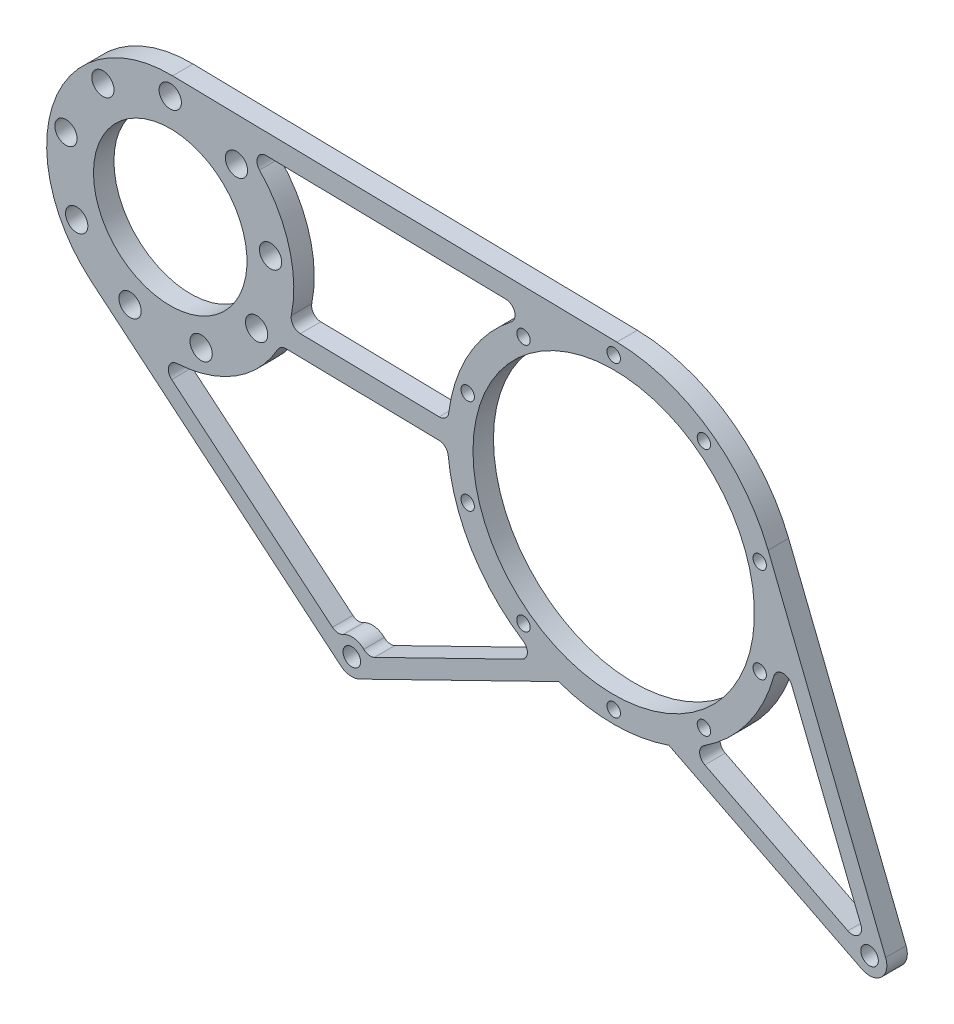
SolidWorks part; units mm, degrees
ref_plane "Front Plane" through (0, 0, 0) normal (0, 0, 1) x (1, 0, 0)
ref_plane "Top Plane" through (0, 0, 0) normal (0, 1, 0) x (1, 0, 0)
ref_plane "Right Plane" through (0, 0, 0) normal (1, 0, 0) x (0, 0, -1)
sketch "Sketch2" plane through (0, 0, 0) normal (0, 0, 1) x (1, 0, 0)
  line L0 (-114.3, 107.95) -> (-114.3, 95.25) construction
  line L1 (-308.8752, 91.6841) -> (-215.9253, 14.1066)
  line L2 (-278.5268, 172.9917) -> (-113.1247, 169.8513)
  line L3 (-13.0706, 21.4387) -> (-56.8054, 130.918)
  line L4 (-208.9705, 13.2659) -> (-134.815, 49.5352)
  line L5 (-21.9498, 13.301) -> (-93.785, 49.5352)
  circle A0 centre (-279.4, 127) radius 28.575
  circle A1 centre (-114.3, 95.25) radius 36 construction
  circle A2 centre (0, 0) radius 12.7 construction
  circle A3 centre (-228.6, 0) radius 12.7 construction
  arc A4 (-278.5268, 172.9917) -> (-308.8752, 91.6841) centre (-279.4, 127) ccw
  arc A5 (-134.815, 49.5352) -> (-93.785, 49.5352) centre (-114.3, 107.95) ccw
  circle A6 centre (-19.05, 19.05) radius 3.2639
  circle A7 centre (-211.7995, 19.05) radius 3.2639
  arc A8 (-215.9253, 14.1066) -> (-208.9705, 13.2659) centre (-211.7995, 19.05) ccw
  arc A9 (-21.9498, 13.301) -> (-13.0706, 21.4387) centre (-19.05, 19.05) ccw
  circle A10 centre (-114.3, 107.95) radius 52.3875
  arc A11 (-56.8054, 130.918) -> (-113.1247, 169.8513) centre (-114.3, 107.95) ccw
  dimension "D1" = 25.4
  dimension "D2" = 25.4
  dimension "D8" = 57.15
  dimension "D9" = 72
  dimension "D10" = 92
  dimension "D12" = 123.825
  dimension "D13" = 6.5278
  dimension "D16" = 6.5278
  dimension "D18" = 3.175
  dimension "D20" = 104.775
  dimension "D3" = 228.6
  dimension "D4" = 114.3
  dimension "D5" = 95.25
  dimension "D6" = 279.4
  dimension "D7" = 127
  dimension "D11" = 12.7
  dimension "D14" = 19.05
  dimension "D15" = 19.05
  dimension "D17" = 25.4
  dimension "D19" = 82.55
extrude "Boss-Extrude1" add sketch "Sketch2" along normal blind 7.62
sketch "Sketch3" plane through (0, 0, 7.62) normal (0, 0, 1) x (1, 0, 0)
  line L0 (-279.4, 127) -> (-279.4, 166.0004) construction
  line L1 (-114.3, 107.95) -> (-114.3, 165.1) construction
  circle A0 centre (-279.4, 127) radius 39.0004 construction
  circle A1 centre (-279.4, 166.0004) radius 4.15
  circle A2 centre (-254.7465, 156.3809) radius 4.15
  circle A3 centre (-242.0442, 133.1649) radius 4.15
  circle A4 centre (-247.2366, 107.2156) radius 4.15
  circle A5 centre (-267.8941, 90.6748) radius 4.15
  circle A6 centre (-294.3509, 91.2822) radius 4.15
  circle A7 centre (-314.2275, 108.7537) radius 4.15
  circle A8 centre (-318.2234, 134.914) radius 4.15
  circle A9 centre (-304.469, 157.5225) radius 4.15
  circle A10 centre (-114.3, 107.95) radius 57.15 construction
  circle A11 centre (-114.3, 165.1) radius 2.5
  circle A12 centre (-80.7081, 154.1853) radius 2.5
  circle A13 centre (-59.9471, 125.6103) radius 2.5
  circle A14 centre (-59.9471, 90.2897) radius 2.5
  circle A15 centre (-80.7081, 61.7147) radius 2.5
  circle A16 centre (-114.3, 50.8) radius 2.5
  circle A17 centre (-147.8919, 61.7147) radius 2.5
  circle A18 centre (-168.6529, 90.2897) radius 2.5
  circle A19 centre (-168.6529, 125.6103) radius 2.5
  circle A20 centre (-147.8919, 154.1853) radius 2.5
  point P24 (-280.288, 127.3232)
  point P48 (-114.3, 107.95)
  dimension "D1" = 78.0009
  dimension "D2" = 8.3
  dimension "D4" = 114.3
  dimension "D5" = 5
  dimension "D3" = 9
  dimension "D6" = 10
extrude "Cut-Extrude1" cut sketch "Sketch3" against normal through all both and the other way through all
sketch "Sketch4" plane through (0, 0, 7.62) normal (0, 0, 1) x (1, 0, 0)
  line L0 (-278.8602, 74.9042) -> (-219.0194, 24.9601)
  line L1 (-48.0193, 91.8071) -> (-22.3039, 27.4349)
  line L2 (-308.8752, 91.6841) -> (-215.9253, 14.1066) construction
  line L3 (-148.3931, 49.9629) -> (-203.3792, 23.0694)
  line L4 (-208.9705, 13.2659) -> (-134.815, 49.5352) construction
  line L5 (-243.5726, 164.7067) -> (-154.4587, 163.0147)
  line L6 (-113.1247, 169.8513) -> (-278.5268, 172.9917) construction
  line L7 (-80.3879, 49.8896) -> (-27.12, 23.021)
  line L8 (-93.785, 49.5352) -> (-21.9498, 13.301) construction
  line L9 (-13.0706, 21.4387) -> (-56.8054, 130.918) construction
  line L10 (-230.9639, 113.6581) -> (-179.2529, 112.6763)
  line L11 (-236.2483, 106.1371) -> (-179.3262, 105.0564)
  arc A0 (-234.3202, 117.8451) -> (-239.355, 104.3639) centre (-279.4, 127) ccw construction
  arc A1 (-175.9167, 101.9055) -> (-175.7218, 115.7294) centre (-114.3, 107.95) ccw construction
  circle A2 centre (-19.05, 19.05) radius 6.4389 construction
  circle A3 centre (-211.7995, 19.05) radius 6.4389 construction
  arc A4 (-278.5268, 172.9917) -> (-308.8752, 91.6841) centre (-279.4, 127) ccw construction
  arc A5 (-246.1625, 158.8004) -> (-234.3202, 117.8451) centre (-279.4, 127) cw
  arc A6 (-152.3771, 156.769) -> (-175.7218, 115.7294) centre (-114.3, 107.95) ccw
  arc A7 (-54.6287, 91.4427) -> (-80.7099, 55.9417) centre (-114.3, 107.95) cw
  arc A8 (-154.4587, 163.0147) -> (-152.3771, 156.769) centre (-154.525, 159.5229) cw
  arc A9 (-243.5726, 164.7067) -> (-246.1625, 158.8004) centre (-243.6389, 161.2148) ccw
  arc A10 (-278.8602, 74.9042) -> (-276.8184, 81.0725) centre (-276.6224, 77.5855) cw
  arc A11 (-148.0251, 56.0292) -> (-148.3931, 49.9629) centre (-149.9276, 53.1003) cw
  arc A12 (-80.3879, 49.8896) -> (-80.7099, 55.9417) centre (-78.8151, 53.0079) cw
  arc A13 (-48.0193, 91.8071) -> (-54.6287, 91.4427) centre (-51.2626, 90.5115) ccw
  arc A14 (-27.12, 23.021) -> (-22.3039, 27.4349) centre (-25.5472, 26.1393) ccw
  arc A15 (-215.0295, 24.6201) -> (-207.3352, 23.69) centre (-211.7995, 19.05) cw
  arc A16 (-203.3792, 23.0694) -> (-207.3352, 23.69) centre (-204.9137, 26.2067) cw
  arc A17 (-219.0194, 24.9601) -> (-215.0295, 24.6201) centre (-216.7815, 27.6414) ccw
  arc A18 (-239.355, 104.3639) -> (-276.8184, 81.0725) centre (-279.4, 127) cw
  arc A19 (-175.9167, 101.9055) -> (-148.0251, 56.0292) centre (-114.3, 107.95) ccw
  arc A20 (-179.3262, 105.0564) -> (-175.9167, 101.9055) centre (-179.3925, 101.5645) cw
  arc A21 (-179.2529, 112.6763) -> (-175.7218, 115.7294) centre (-179.1866, 116.1682) ccw
  arc A22 (-230.9639, 113.6581) -> (-234.3202, 117.8451) centre (-230.8976, 117.15) cw
  arc A23 (-236.2483, 106.1371) -> (-239.355, 104.3639) centre (-236.3146, 102.6452) ccw
  point P40 (-253.319, 164.8917)
  point P43 (-286.9018, 81.6158)
  point P46 (-142.5125, 52.8391)
  point P50 (-52.5701, 103.1988)
  point P56 (-216.7994, 23.1072)
  dimension "D1" = 61.9125
  dimension "D2" = 12.8778
  dimension "D3" = 12.8778
  dimension "D9" = 3.4925
  dimension "D10" = 61.9125
  dimension "D11" = 3.4925
  dimension "D14" = 3.4925
  dimension "D4" = 6.35
  dimension "D5" = 6.35
  dimension "D6" = 7.62
  dimension "D7" = 6.35
  dimension "D8" = 6.35
  dimension "D12" = 50.8
  dimension "D13" = 7.62
extrude "Cut-Extrude2" cut sketch "Sketch4" against normal through all both and the other way through all
